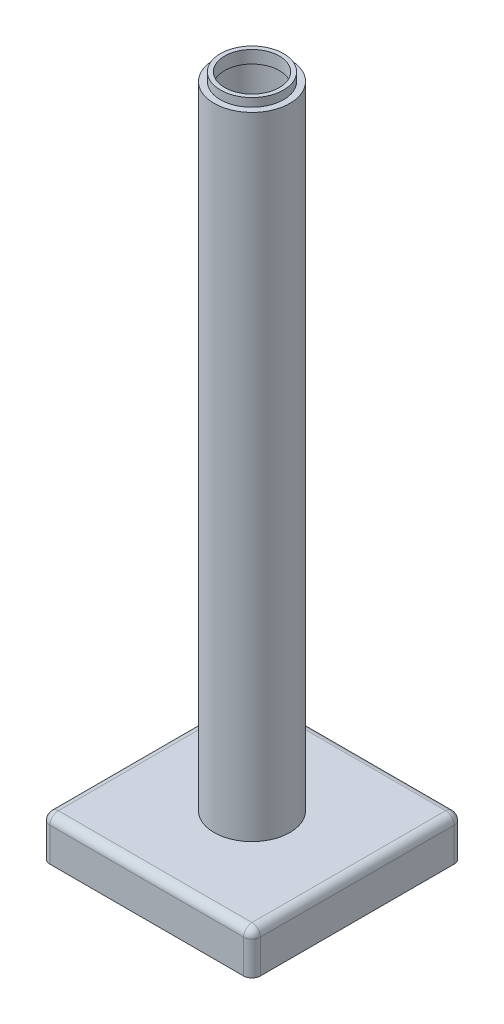
SolidWorks part; units mm, degrees
ref_plane "前视基准面" through (0, 0, 0) normal (0, 0, 1) x (1, 0, 0)
ref_plane "上视基准面" through (0, 0, 0) normal (0, 1, 0) x (1, 0, 0)
ref_plane "右视基准面" through (0, 0, 0) normal (1, 0, 0) x (0, 0, -1)
other "Configuration Table"
sketch "底座" plane through (0, 0, 0) normal (0, 1, 0) x (1, 0, 0)
  line L5 (-25, -25) -> (25, -25)
  line L6 (-25, -25) -> (-25, 25)
  line L7 (-25, 25) -> (25, 25)
  line L8 (25, -25) -> (25, 25)
  line L9 (-25, -25) -> (25, 25) construction
  line L10 (-25, 25) -> (25, -25) construction
  circle A1 centre (0, 0) radius 7.5
  point P0 (0, 0)
  dimension "D3" = 15
  dimension "D1" = 50
  dimension "D2" = 50
extrude "凸台-拉伸1" add sketch "底座" along normal blind 10
fillet "圆角2" radius 2 8 edges at (0, 10, 25) (-25, 10, 0) (0, 10, -25) (25, 10, 0) (-25, 5, -25) (25, 5, -25) (25, 5, 25) (-25, 5, 25)
sketch "圆柱" plane through (0, 10, 0) normal (0, 1, 0) x (1, 0, 0)
  circle A1 centre (0, 0) radius 9
extrude "凸台-拉伸2" add sketch "圆柱" along normal blind 150 separate body
shell "抽壳6" thickness 1.5 removed face at (0, 160, 9) removed face at (0, 10, 9)
ref_plane "基准面3" through (0, 159, 0) normal (0, 1, 0) x (1, 0, 0)
sketch "草图6" plane through (0, 159, 0) normal (0, 1, 0) x (1, 0, 0)
  circle A0 centre (0, 0) radius 7.5 construction
  circle A1 centre (0, 0) radius 7.5
extrude "凸台-拉伸5" add sketch "草图6" along normal blind 3
shell "抽壳13" thickness 1 removed face at (0, 159, 7.5) removed face at (0, 162, 7.5)
ref_plane "基准面4" through (0, 0, 0) normal (0, 0, -1) x (-1, 0, 0)
sketch "草图7" plane through (0, 0, 0) normal (0, 0, -1) x (-1, 0, 0)
  line L0 (0, 0) -> (7.5, 0) construction
  line L1 (55, 0) -> (-55, 0) construction
  line L2 (7.5, 0) -> (9, 0) construction
  line L3 (9, 10.0683) -> (9, 0) construction
  line L4 (7.5, 0) -> (7.5, 50000) construction
  line L5 (6.5, 247.0194) -> (6.5, 244.0194) construction
  dimension "D1" = 7.5
  dimension "D2" = 1.5
  dimension "D3" = 3
  dimension "D4" = 1
ref_plane "基准面5" through (0, 0, 0) normal (0, -1, 0) x (-1, 0, 0)
sketch "草图9" plane through (0, 0, 0) normal (0, -1, 0) x (-1, 0, 0)
  line L0 (0, 25) -> (0, -25) construction
  line L1 (-23, 25) -> (23, 25) construction
  line L2 (23, -25) -> (-23, -25) construction
  line L4 (-4, 5.1555) -> (4, 5.1555)
  line L5 (-4, 5.1555) -> (-4, 25)
  line L6 (-4, 25) -> (4, 25)
  line L7 (4, 5.1555) -> (4, 25)
  line L8 (-4, 5.1555) -> (4, 25) construction
  line L9 (-4, 25) -> (4, 5.1555) construction
  point P6 (0, 15.0777)
  dimension "D1" = 8
extrude "切除-拉伸1" cut sketch "草图9" against normal blind 7
